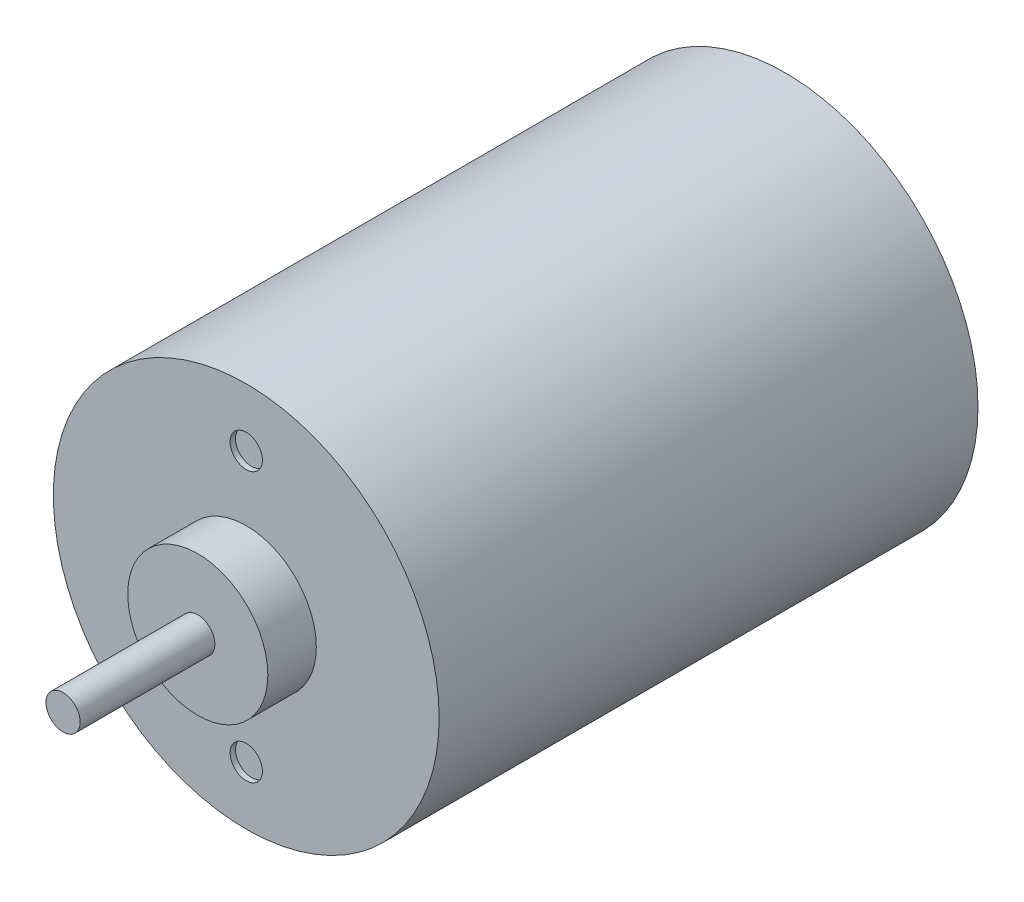
SolidWorks part; units mm, degrees
ref_plane "正面" through (0, 0, 0) normal (0, 0, 1) x (1, 0, 0)
ref_plane "平面" through (0, 0, 0) normal (0, 1, 0) x (1, 0, 0)
ref_plane "右側面" through (0, 0, 0) normal (1, 0, 0) x (0, 0, -1)
sketch "ｽｹｯﾁ2" plane through (0, 0, 0) normal (0, 0, 1) x (1, 0, 0)
  circle A0 centre (0, 0) radius 17.9
  dimension "D1" = 35.8
extrude "ﾎﾞｽ - 押し出し1" add sketch "ｽｹｯﾁ2" along normal blind 50
sketch "ｽｹｯﾁ3" plane through (0, 0, 50) normal (0, 0, 1) x (1, 0, 0)
  circle A0 centre (0, 0) radius 6.5
  dimension "D1" = 13
extrude "ﾎﾞｽ - 押し出し2" add sketch "ｽｹｯﾁ3" along normal blind 4.5
sketch "ｽｹｯﾁ4" plane through (0, 0, 54.5) normal (0, 0, 1) x (1, 0, 0)
  circle A0 centre (0, 0) radius 1.585
  dimension "D1" = 3.17
extrude "ﾎﾞｽ - 押し出し5" add sketch "ｽｹｯﾁ4" along normal blind 12.5
sketch "ｽｹｯﾁ5" plane through (0, 0, 50) normal (0, 0, 1) x (1, 0, 0)
  circle A0 centre (0, 12.5) radius 1.5
  circle A1 centre (0, -12.5) radius 1.5
  point P4 (0, 0)
  point P6 (0, 0)
  dimension "D1" = 3
  dimension "D2" = 25
  dimension "D3" = 12.5
extrude "ｶｯﾄ - 押し出し1" cut sketch "ｽｹｯﾁ5" against normal blind 0.5
